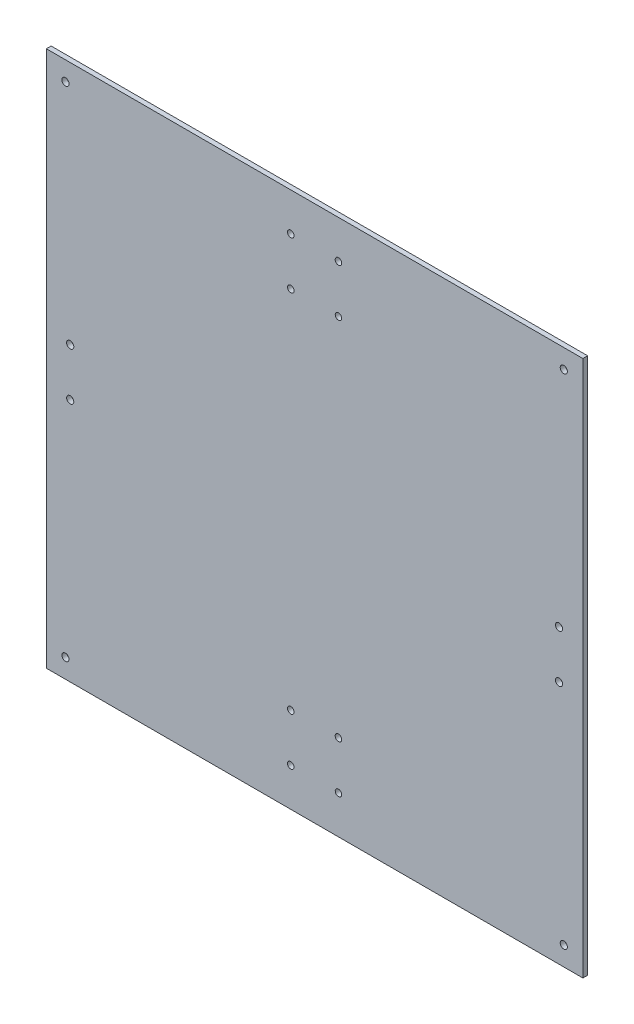
SolidWorks part; units mm, degrees
ref_plane "Front Plane" through (0, 0, 0) normal (0, 0, 1) x (1, 0, 0)
ref_plane "Top Plane" through (0, 0, 0) normal (0, 1, 0) x (1, 0, 0)
ref_plane "Right Plane" through (0, 0, 0) normal (1, 0, 0) x (0, 0, -1)
sketch "Sketch1" plane through (0, 0, 0) normal (0, 0, 1) x (1, 0, 0)
  line L0 (21, -186.5) -> (16, -186.5) construction
  line L1 (112.5, 26) -> (-112.5, 26)
  line L2 (112.5, 26) -> (112.5, -199)
  line L3 (112.5, -199) -> (-112.5, -199)
  line L4 (-112.5, 26) -> (-112.5, -199)
  line L5 (-16, -13) -> (-16, 13) construction
  line L7 (16, 13) -> (16, -13) construction
  line L9 (-16, 13.5) -> (16, 13.5) construction
  line L10 (0, 26) -> (0, -199) construction
  line L12 (104.5, 18) -> (-104.5, 18)
  line L13 (104.5, 18) -> (104.5, -191)
  line L14 (104.5, -191) -> (-104.5, -191)
  line L15 (-104.5, 18) -> (-104.5, -191)
  circle A0 centre (10, -10) radius 1.35
  circle A1 centre (-10, -10) radius 1.375
  circle A2 centre (-10, 10) radius 1.375
  circle A3 centre (10, 10) radius 1.375
  circle A4 centre (10, -183) radius 1.35
  circle A5 centre (-10, -183) radius 1.375
  circle A6 centre (-10, -163) radius 1.375
  circle A7 centre (10, -163) radius 1.375
  circle A8 centre (102.5, -76.5) radius 1.5
  circle A9 centre (102.5, -96.5) radius 1.5
  circle A10 centre (-102.5, -76.5) radius 1.5
  circle A11 centre (-102.5, -96.5) radius 1.5
  circle A12 centre (104.5, 18) radius 1.5
  circle A13 centre (104.5, -191) radius 1.5
  circle A14 centre (-104.5, -191) radius 1.5
  circle A15 centre (-104.5, 18) radius 1.5
  dimension "D7" = 3
  dimension "D8" = 3
  dimension "D9" = 20
  dimension "D11" = 10
  dimension "D12" = 10
  dimension "D13" = 3
  dimension "D14" = 3
  dimension "D15" = 3
  dimension "D16" = 3
  dimension "D1" = 225
  dimension "D2" = 225
  dimension "D3" = 12.5
  dimension "D4" = 96.5
  dimension "D5" = 96.5
  dimension "D6" = 12.5
  dimension "D10" = 102.5
  dimension "D17" = 209
  dimension "D18" = 209
  dimension "D19" = 8
  dimension "D20" = 8
  dimension "D21" = 8
  dimension "D22" = 8
extrude "Boss-Extrude1" add sketch "Sketch1" along normal blind 2 contours L10 L12 A15 L15 A14 L14 A10 A6 A5 A2 A1 A11 | L10 L1 L4 L3 L14 A14 L15 A15 L12 | L12 L10 L14 A13 L13 A12 A0 A3 A4 A7 A8 A9 | L1 L10 L12 A12 L13 A13 L14 L3 L2 region at (109.9844, -86.5, 0) region at (-2.5156, 22, 0) region at (52.2543, -86.5002, 0) region at (-52.2551, -86.5, 0)
